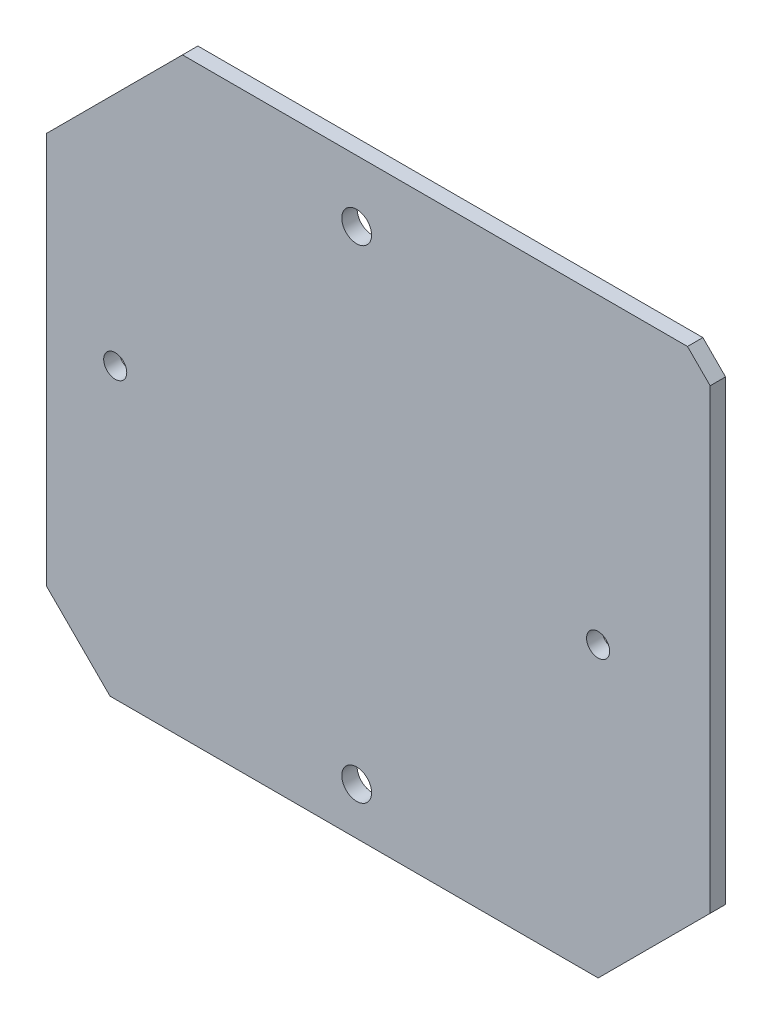
SolidWorks part; units mm, degrees
material "FR4_stuffedProtoboard"
ref_plane "Front Plane" through (0, 0, 0) normal (0, 0, 1) x (1, 0, 0)
ref_plane "Top Plane" through (0, 0, 0) normal (0, 1, 0) x (1, 0, 0)
ref_plane "Right Plane" through (0, 0, 0) normal (1, 0, 0) x (0, 0, -1)
sketch "Imported DXF" plane through (0, 0, 0) normal (0, 0, 1) x (1, 0, 0)
  line L0 (34.372, 27.4613) -> (36.628, 25.2053) construction
  line L1 (36.75, 24.9108) -> (36.75, -22.2441) construction
  line L2 (36.628, -22.5387) -> (25.2053, -33.9613) construction
  line L3 (24.9107, -34.0833) -> (-25.5774, -34.0833) construction
  line L4 (-25.872, -33.9613) -> (-32.2947, -27.5387) construction
  line L5 (-32.4168, -27.2454) -> (-32.429, 13.2331) construction
  line L6 (-32.307, 13.5263) -> (-18.372, 27.4613) construction
  line L7 (-19.8333, 19.5) -> (-19.1667, 19.5) construction
  line L8 (-19.5, 19.8333) -> (-19.5, 19.1667) construction
  line L9 (-19.3333, 19.6667) -> (-18.3333, 20.6667) construction
  line L10 (-19.6667, 19.3333) -> (-20.5833, 18.4167) construction
  line L11 (-19.3333, 19.3333) -> (-18.9167, 18.9167) construction
  line L12 (19.5, 19.8333) -> (19.5, 19.1667) construction
  line L13 (19.8333, 19.5) -> (19.1667, 19.5) construction
  line L14 (19.6667, 19.3333) -> (20.6667, 18.3333) construction
  line L15 (19.3333, 19.6667) -> (18.4167, 20.5833) construction
  line L16 (19.3333, 19.3333) -> (18.9167, 18.9167) construction
  line L17 (-19.8333, -19.5) -> (-19.1667, -19.5) construction
  line L18 (-19.5, -19.8333) -> (-19.5, -19.1667) construction
  line L19 (-19.3333, -19.6667) -> (-18.3333, -20.6667) construction
  line L20 (-19.6667, -19.3333) -> (-20.5833, -18.4167) construction
  line L21 (-19.3333, -19.3333) -> (-18.9167, -18.9167) construction
  line L22 (19.8333, -19.5) -> (19.1667, -19.5) construction
  line L23 (19.5, -19.8333) -> (19.5, -19.1667) construction
  line L24 (19.3333, -19.6667) -> (18.3333, -20.6667) construction
  line L25 (19.6667, -19.3333) -> (20.5833, -18.4167) construction
  line L26 (19.3333, -19.3333) -> (18.9167, -18.9167) construction
  line L27 (31.9857, 21.9857) -> (31.5143, 21.5143) construction
  line L28 (31.9857, 21.5143) -> (31.5143, 21.9857) construction
  line L29 (31.75, 21.5143) -> (31.75, 20.1001) construction
  line L30 (31.75, 21.9857) -> (31.75, 23.2821) construction
  line L31 (31.5143, 21.75) -> (30.9251, 21.75) construction
  line L32 (34.0774, 27.5833) -> (-18.0774, 27.5833) construction
  line L33 (-63.5042, 0) -> (63.5042, 0) construction
  line L34 (0, 54.0232) -> (0, -54.9661) construction
  arc A0 (34.372, 27.4613) -> (34.0774, 27.5833) centre (34.0774, 27.1667) ccw construction
  arc A1 (36.75, 24.9108) -> (36.628, 25.2054) centre (36.3333, 24.9108) ccw construction
  arc A2 (36.628, -22.5387) -> (36.75, -22.2441) centre (36.3333, -22.2441) ccw construction
  arc A3 (24.9107, -34.0833) -> (25.2054, -33.9613) centre (24.9107, -33.6667) ccw construction
  arc A4 (-25.872, -33.9613) -> (-25.5774, -34.0833) centre (-25.5774, -33.6667) ccw construction
  arc A5 (-32.4168, -27.2454) -> (-32.2947, -27.5386) centre (-32.0001, -27.244) ccw construction
  arc A6 (-32.307, 13.5263) -> (-32.4291, 13.2331) centre (-32.0129, 13.2319) ccw construction
  arc A7 (-18.0774, 27.5833) -> (-18.372, 27.4613) centre (-18.0774, 27.1667) ccw construction
  circle A8 centre (-20.9167, 0) radius 1 construction
  circle A9 centre (20.9167, 0) radius 1 construction
  circle A10 centre (0, 20.9167) radius 1.2917 construction
  circle A11 centre (0, -20.9167) radius 1.2917 construction
  point P93 (0, 0)
  point P94 (0, 0)
  point P95 (0, 0)
  point P96 (0, 0)
  dimension "D1" = 2
sketch "Outline" plane through (0, 0, 0) normal (0, 0, 1) x (1, 0, 0)
  line L0 (34.3921, 31.5) -> (36.75, 29.1421)
  line L1 (36.75, 29.1421) -> (36.75, -18.3579)
  line L2 (36.75, -18.3579) -> (25.1079, -30)
  line L3 (25.1079, -30) -> (-25.6421, -30)
  line L4 (-25.6421, -30) -> (-32.25, -23.3921)
  line L5 (-32.25, -23.3921) -> (-32.25, 17.3579)
  line L6 (-32.25, 17.3579) -> (-18.1079, 31.5)
  line L32 (103.1538, 0) -> (-30.8725, 0) construction
  line L33 (0, 82.654) -> (0, -12.3574) construction
  line L34 (34.3921, 31.5) -> (-18.1079, 31.5)
  point P0 (0, 0)
  point P2 (0, 0)
  point P4 (0, 0)
  point P5 (0, 0)
  dimension "D2" = 135
  dimension "D3" = 135
  dimension "D4" = 135
  dimension "D5" = 47.5
  dimension "D6" = 135
  dimension "D7" = 36.75
  dimension "D8" = 30
  dimension "D9" = 50.75
  dimension "D10" = 40.75
  dimension "D11" = 52.5
  dimension "D12" = 20
  dimension "D20" = 69
sketch "Connector locations" plane through (0, 0, 0) normal (0, 0, 1) x (1, 0, 0)
  line L0 (31.8, 27.4) -> (31.8, 24.2)
  line L1 (23.7588, 21.496) -> (21.496, 23.7588)
  line L2 (36.75, 29.1421) -> (36.75, -18.3579) construction
  line L3 (34.3921, 31.5) -> (-18.1079, 31.5) construction
  line L4 (0, 0) -> (22.6274, 22.6274) construction
  line L5 (200103.1538, 0) -> (-200030.8725, 0) construction
  line L6 (21.496, -23.7588) -> (23.7588, -21.496)
  line L7 (-23.7588, -21.496) -> (-21.496, -23.7588)
  line L8 (-21.496, 23.7588) -> (-23.7588, 21.496)
  dimension "D1" = 4.95
  dimension "D2" = 3.2
  dimension "D3" = 4.1
  dimension "D4" = 32
  dimension "D5" = 4
  dimension "D6" = 3.2
  dimension "D7" = 45
  dimension "D8" = 45
extrude "Boss-Extrude3" add sketch "Outline" against normal blind 1.6
sketch "Hole Locations" plane through (0, 0, 0) normal (0, 0, 1) x (1, 0, 0)
  circle A1 centre (-25.1, 0) radius 1.2 construction
  circle A2 centre (0, 25.1) radius 1.55 construction
  circle A3 centre (25.1, 0) radius 1.2 construction
  circle A4 centre (0, -25.1) radius 1.55 construction
  circle A5 centre (-25.1, 0) radius 1.2
  circle A6 centre (0, 25.1) radius 1.55
  circle A7 centre (25.1, 0) radius 1.2
  circle A8 centre (0, -25.1) radius 1.55
extrude "Cut-Extrude1" cut sketch "Hole Locations" against normal up to next
